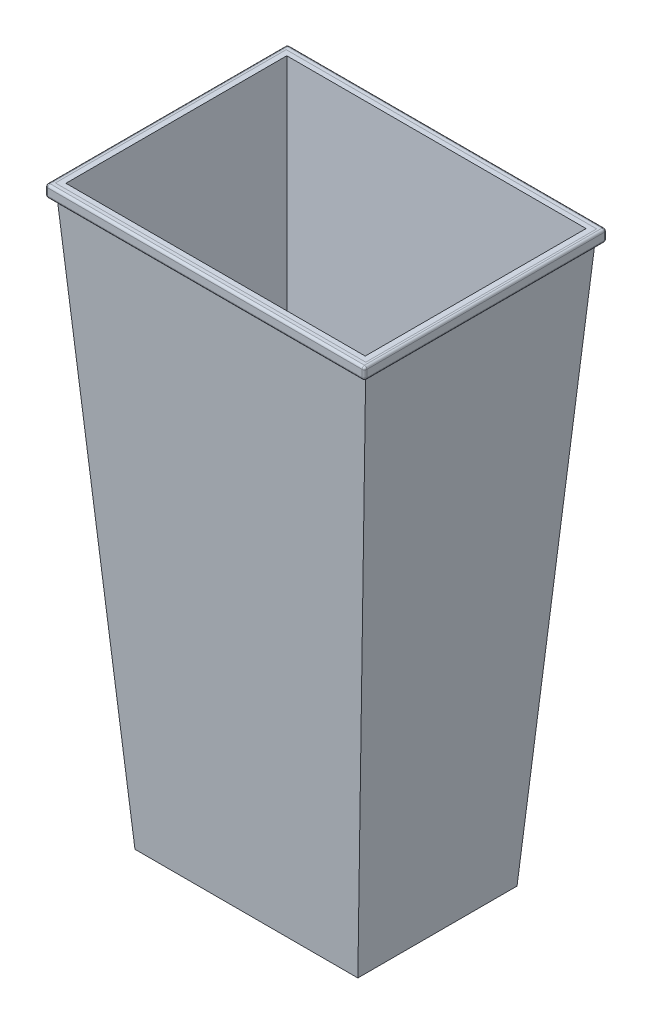
SolidWorks part; units mm, degrees
ref_plane "Alzado" through (0, 0, 0) normal (0, 0, 1) x (1, 0, 0)
ref_plane "Planta" through (0, 0, 0) normal (0, 1, 0) x (1, 0, 0)
ref_plane "Vista lateral" through (0, 0, 0) normal (1, 0, 0) x (0, 0, -1)
sketch "Croquis1" plane through (0, 0, 0) normal (0, 1, 0) x (1, 0, 0)
  line L1 (-140, 100) -> (140, 100)
  line L2 (-140, 100) -> (-140, -100)
  line L3 (-140, -100) -> (140, -100)
  line L4 (140, 100) -> (140, -100)
  line L5 (-140, 100) -> (140, -100) construction
  line L6 (-140, -100) -> (140, 100) construction
  point P0 (0, 0)
  dimension "D1" = 280
  dimension "D2" = 200
extrude "Saliente-Extruir1" add sketch "Croquis1" along normal blind 10
ref_plane "Plano1" through (0, 720, 0) normal (0, 1, 0) x (1, 0, 0)
sketch "Croquis2" plane through (0, 720, 0) normal (0, 1, 0) x (1, 0, 0)
  line L1 (-195, 145) -> (195, 145)
  line L2 (-195, 145) -> (-195, -145)
  line L3 (-195, -145) -> (195, -145)
  line L4 (195, 145) -> (195, -145)
  line L5 (-195, 145) -> (195, -145) construction
  line L6 (-195, -145) -> (195, 145) construction
  point P0 (0, 0)
  dimension "D1" = 390
  dimension "D2" = 290
loft "Recubrir2" add profiles "Croquis1<2>", "Croquis2" connector at (-140, 0, -100) connector at (-195, 720, -145)
sketch "Croquis1<2>" plane through (0, 0, 0) normal (0, 1, 0) x (1, 0, 0) same geometry as "Croquis1"
sketch "Croquis3" plane through (0, 720, 0) normal (0, 1, 0) x (1, 0, 0)
  line L1 (-188.0022, 138.7358) -> (188.0022, 138.7358)
  line L2 (-188.0022, 138.7358) -> (-188.0022, -138.7358)
  line L3 (-188.0022, -138.7358) -> (188.0022, -138.7358)
  line L4 (188.0022, 138.7358) -> (188.0022, -138.7358)
  line L5 (-188.0022, 138.7358) -> (188.0022, -138.7358) construction
  line L6 (-188.0022, -138.7358) -> (188.0022, 138.7358) construction
  point P0 (0, 0)
  point P6 (188.0022, 138.7358)
extrude "Cortar-Extruir1" cut sketch "Croquis3" against normal blind 710 draft 4
sketch "Croquis4" plane through (0, 720, 0) normal (0, 1, 0) x (1, 0, 0)
  line L1 (-200.525, 152.1296) -> (200.525, 152.1296)
  line L2 (-200.525, 152.1296) -> (-200.525, -152.1296)
  line L3 (-200.525, -152.1296) -> (200.525, -152.1296)
  line L4 (200.525, 152.1296) -> (200.525, -152.1296)
  line L5 (-200.525, 152.1296) -> (200.525, -152.1296) construction
  line L6 (-200.525, -152.1296) -> (200.525, 152.1296) construction
  line L7 (-195, 145) -> (195, 145)
  line L8 (-195, 145) -> (-195, -145)
  line L9 (-195, -145) -> (195, -145)
  line L10 (195, 145) -> (195, -145)
  line L11 (-195, 145) -> (195, -145) construction
  line L12 (-195, -145) -> (195, 145) construction
  point P0 (0, 0)
  point P6 (0, 0)
extrude "Saliente-Extruir2" add sketch "Croquis4" against normal blind 15 separate body
fillet "Redondeo1" radius 3 12 edges at (200.525, 712.5, -152.1296) (0, 705, -152.1296) (0, 720, -152.1296) (-200.525, 712.5, -152.1296) (-200.525, 712.5, 152.1296) (200.525, 712.5, 152.1296) (200.525, 705, 0) (200.525, 720, 0) (-200.525, 705, 0) (0, 705, 152.1296) (-200.525, 720, 0) (0, 720, 152.1296)
